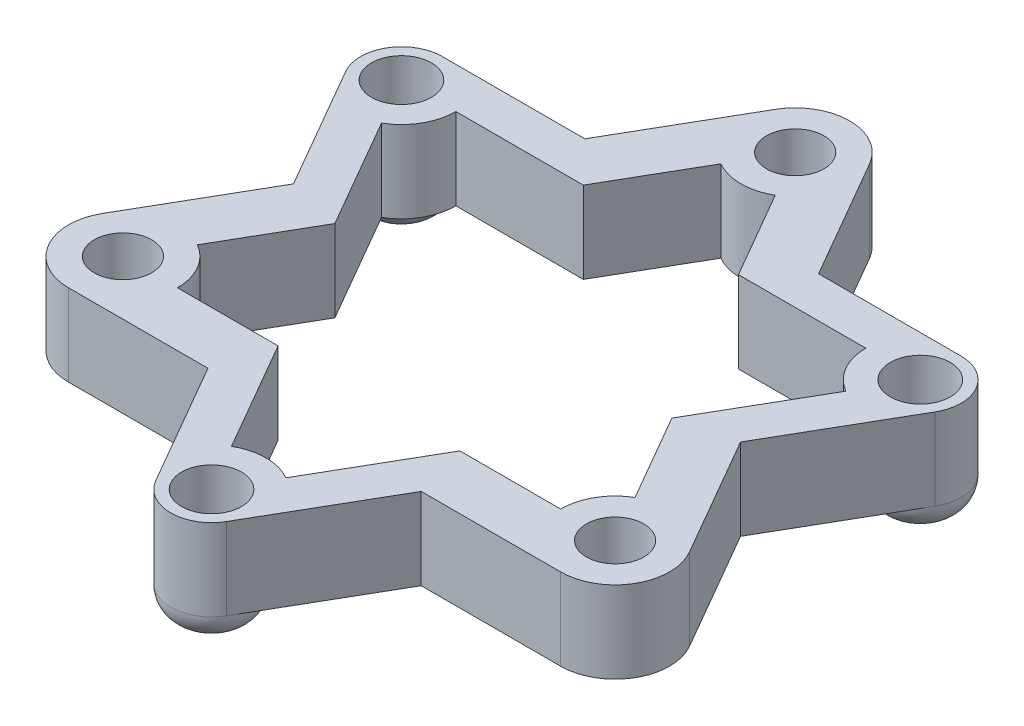
SolidWorks part; units mm, degrees
ref_plane "Front Plane" through (0, 0, 0) normal (0, 0, 1) x (1, 0, 0)
ref_plane "Top Plane" through (0, 0, 0) normal (0, 1, 0) x (1, 0, 0)
ref_plane "Right Plane" through (0, 0, 0) normal (1, 0, 0) x (0, 0, -1)
sketch "Sketch1" plane through (0, 0, 0) normal (0, 1, 0) x (1, 0, 0)
  line L0 (0, 0) -> (9.0359, 0)
  line L1 (10.7679, 3) -> (1.7321, 18.6506)
  line L2 (-1.7321, 18.6506) -> (-10.7679, 3)
  line L3 (-9.0359, 0) -> (0, 0)
  arc A0 (9.0359, 0) -> (10.7679, 3) centre (9.0359, 2) ccw
  arc A1 (-10.7679, 3) -> (-9.0359, 0) centre (-9.0359, 2) ccw
  arc A2 (1.7321, 18.6506) -> (-1.7321, 18.6506) centre (0, 17.6506) ccw
  circle A3 centre (0, 17.6506) radius 1.054
  circle A4 centre (-9.0359, 2) radius 1.054
  circle A5 centre (9.0359, 2) radius 1.054
  point P7 (12.5, 0)
  point P10 (-12.5, 0)
  point P13 (0, 21.6506)
  dimension "D5" = 2
  dimension "D1" = 60
  dimension "D2" = 60
  dimension "D3" = 25
  dimension "D4" = 12.5
extrude "Boss-Extrude1" add sketch "Sketch1" along normal blind 3
ref_point "Point1"
ref_axis "Axis1" through (0, 3, -7.2169) along (0, 1, 0)
sketch "Sketch3" plane through (0, 3, 0) normal (0, 1, 0) x (1, 0, 0)
  line L0 (-9.5263, 14.2169) -> (9.5263, 14.2169)
  line L1 (-1.299, -4.5331) -> (-10.8253, 11.9669)
  line L2 (1.299, -4.5331) -> (10.8253, 11.9669)
  arc A0 (-1.299, -4.5331) -> (1.299, -4.5331) centre (0, -3.7831) ccw
  circle A1 centre (0, -3.7831) radius 1.1
  arc A2 (-9.5263, 14.2169) -> (-10.8253, 11.9669) centre (-9.5263, 12.7169) ccw
  circle A3 centre (-9.5263, 12.7169) radius 1.1
  arc A4 (10.8253, 11.9669) -> (9.5263, 14.2169) centre (9.5263, 12.7169) ccw
  circle A5 centre (9.5263, 12.7169) radius 1.1
  point P14 (0, 7.2169)
  dimension "D1" = 11
  dimension "D2" = 3
extrude "Boss-Extrude2" add sketch "Sketch3" against normal up to surface (3 mm away) up to face at (-9.0359, 0, -0.946)
sketch "Sketch2" plane through (0, 3, 0) normal (0, 1, 0) x (1, 0, 0)
  line L0 (-1, 15.9186) -> (-2.8485, 12.7169)
  line L1 (-7.0359, 2) -> (-3.3389, 2)
  line L2 (8.0359, 3.7321) -> (6.1874, 6.9338)
  line L3 (8.5263, 10.9848) -> (6.1874, 6.9338)
  line L4 (-1, -2.0511) -> (-3.3389, 2)
  line L5 (-7.5263, 12.7169) -> (-2.8485, 12.7169)
  line L6 (-6.1874, 6.9338) -> (-8.0359, 3.7321)
  line L7 (2.8485, 12.7169) -> (1, 15.9186)
  line L8 (3.3389, 2) -> (7.0359, 2)
  line L9 (-6.1874, 6.9338) -> (-8.5263, 10.9848)
  line L10 (3.3389, 2) -> (1, -2.0511)
  line L11 (2.8485, 12.7169) -> (7.5263, 12.7169)
  arc A0 (-1, 15.9186) -> (1, 15.9186) centre (0, 17.6506) ccw
  arc A1 (8.0359, 3.7321) -> (7.0359, 2) centre (9.0359, 2) ccw
  arc A2 (-7.0359, 2) -> (-8.0359, 3.7321) centre (-9.0359, 2) ccw
  arc A3 (-8.5263, 10.9848) -> (-7.5263, 12.7169) centre (-9.5263, 12.7169) ccw
  arc A4 (7.5263, 12.7169) -> (8.5263, 10.9848) centre (9.5263, 12.7169) ccw
  arc A5 (1, -2.0511) -> (-1, -2.0511) centre (0, -3.7831) ccw
extrude "Cut-Extrude1" cut sketch "Sketch2" against normal through all
sketch "Sketch4" plane through (0, 0, 0) normal (0, -1, 0) x (1, 0, 0)
  circle A0 centre (0, 3.7831) radius 1.5
  circle A1 centre (9.5263, -12.7169) radius 1.5
  circle A2 centre (-9.5263, -12.7169) radius 1.5
extrude "Boss-Extrude3" add sketch "Sketch4" along normal blind 1
fillet "Fillet1" radius 1 3 edges at (-9.5263, -1, -14.2169) (9.5263, -1, -14.2169) (0, -1, 2.2831)
